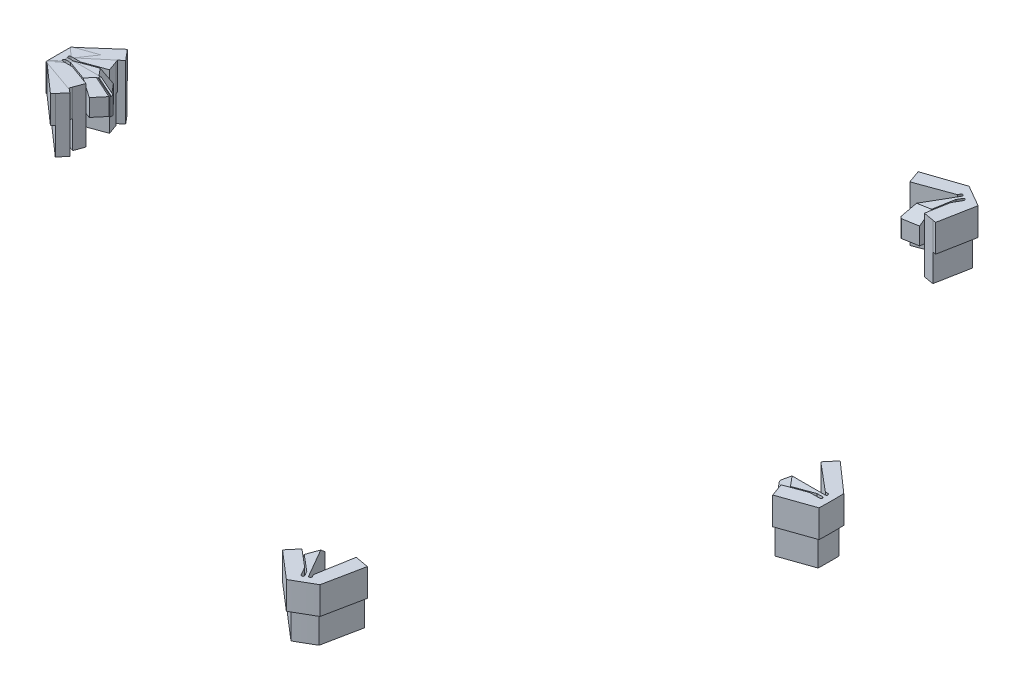
SolidWorks part; units mm, degrees
ref_plane "前视基准面" through (0, 0, 0) normal (0, 0, 1) x (1, 0, 0)
ref_plane "上视基准面" through (0, 0, 0) normal (0, 1, 0) x (1, 0, 0)
ref_plane "右视基准面" through (0, 0, 0) normal (1, 0, 0) x (0, 0, -1)
other "Configuration Table"
sketch "草图1" plane through (0, 0, 0) normal (0, 1, 0) x (1, 0, 0)
  line L0 (-106.6702, 0) -> (227.8, 0) construction
  line L1 (97, 0) -> (109.5607, 0) construction
  line L2 (109.5607, 0) -> (99.9387, 3.5022) construction
  line L3 (109.5607, 0) -> (99.9387, 8.0739) construction
  line L4 (99.9387, 8.0739) -> (99.9387, 3.5022) construction
  line L5 (109.5607, 0) -> (99.9387, -3.5022) construction
  line L6 (97, 0) -> (99.9387, -3.5022)
  line L7 (97, 0) -> (97, 0.4)
  line L8 (97, 0.4) -> (109.5607, 0.4)
  line L9 (109.5607, 0.4) -> (109.5607, 0) construction
  line L10 (109.5607, 0) -> (109.5607, -0.4) construction
  line L11 (109.5607, -0.4) -> (108.4618, -0.4)
  line L12 (109.5607, 0.4) -> (110.3607, 0.4)
  line L13 (110.3607, 0.4) -> (110.3607, -0.4)
  line L14 (110.3607, -0.4) -> (109.5607, -0.4)
  line L15 (108.4618, -0.4) -> (99.9387, -3.5022)
  circle A0 centre (0, 0) radius 97 construction
  circle A1 centre (0, 0) radius 100 construction
  circle A2 centre (109.5607, 0) radius 12.5607 construction
  circle A3 centre (109.5607, 0) radius 10.2396 construction
  dimension "D1" = 200
  dimension "D2" = 194
  dimension "D3" = 20
  dimension "D4" = 20
  dimension "D5" = 20
  dimension "D6" = 0.4
  dimension "D7" = 0.8
extrude "凸台-拉伸1" add sketch "草图1" along normal blind 8
sketch "草图2" plane through (0, 0, 0) normal (0, 1, 0) x (1, 0, 0)
  line L0 (115.245, 0) -> (-162.7444, 0) construction
  line L1 (108.4618, -0.4) -> (109.5607, 0) construction
  line L2 (99.9387, -3.5022) -> (108.4618, -0.4) construction
  line L3 (109.5607, 0) -> (101.1351, 7.0699) construction
  line L4 (100.981, 8.1131) -> (109.2196, 1.2)
  line L5 (109.2196, 1.2) -> (110.3607, 1.2) construction
  line L6 (110.3607, 1.2) -> (110.3607, -1.2) construction
  line L7 (110.3607, -1.2) -> (107.1409, -1.2) construction
  line L8 (107.1409, -1.2) -> (100.981, -3.442)
  line L9 (100.981, -3.442) -> (102.007, -6.2611)
  line L10 (102.007, -6.2611) -> (111.3203, -2.9997)
  line L12 (111.3203, 2.9997) -> (102.9093, 10.4112)
  line L13 (102.9093, 10.4112) -> (100.981, 8.1131)
  line L14 (107.1409, -1.2) -> (109.9607, -1.2)
  line L15 (110.3607, 0.4) -> (97, 0.4) construction
  line L16 (108.4618, -0.4) -> (110.3607, -0.4) construction
  line L17 (109.9607, -0.4) -> (110.3607, -0.4)
  line L18 (110.3607, -0.4) -> (110.3607, 0.4)
  line L19 (110.3607, 0.4) -> (109.9607, 0.4)
  line L20 (109.9607, 1.2) -> (109.2196, 1.2)
  line L21 (111.3607, 0) -> (110.3607, 0) construction
  arc A2 (109.9607, 1.2) -> (109.9607, 0.4) centre (109.9607, 0.8) cw
  arc A3 (109.9607, -0.4) -> (109.9607, -1.2) centre (109.9607, -0.8) cw
  arc A4 (111.3203, -2.9997) -> (111.3203, 2.9997) centre (0, 0) ccw
  circle A5 centre (111.3607, 0) radius 3 construction
  dimension "D10" = 6
  dimension "D1" = 0.7
  dimension "D2" = 0.3
  dimension "D3" = 0.8
  dimension "D4" = 0.8
  dimension "D5" = 1
  dimension "D6" = 3
  dimension "D7" = 3
  dimension "D8" = 1
  dimension "D9" = 40
extrude "凸台-拉伸2" add sketch "草图2" along normal blind 8 and the other way blind 8
sketch "草图4" plane through (12.8162, 0, 35.2121) normal (0.342, 0, 0.9397) x (0.9397, 0, -0.342)
  line L0 (92.7138, 5) -> (95.7138, 8)
  line L1 (92.7138, 8) -> (92.7138, 0) construction
  line L2 (92.7138, 8) -> (101.7839, 8) construction
  line L3 (95.7138, 8) -> (92.7138, 8)
  line L4 (92.7138, 8) -> (92.7138, 5)
  dimension "D1" = 5
  dimension "D2" = 45
extrude "切除-拉伸1" cut sketch "草图4" along direction (0.6428, 0, 0.766) on the side against the normal up to surface (3.7545 mm away) up to face at (103.4804, 4, -0.4)
ref_plane "基准面1" through (88.9113, 0, -31.1355) normal (0.9438, 0, -0.3305) x (0, 1, 0)
sketch "草图10" plane through (88.9113, 0, -31.1355) normal (0.9438, 0, -0.3305) x (0, 1, 0)
  line L0 (0, 34.5946) -> (0, 48.0374) construction
  line L1 (0, 32.0591) -> (0, 36.3357) construction
  line L3 (-8, 39.6233) -> (8, 39.6233) construction
  line L4 (0, 40.6233) -> (0, 39.6233)
  line L5 (0, 39.6233) -> (8, 39.6233)
  line L6 (8, 39.6233) -> (8, 40.6233)
  line L7 (8, 40.6233) -> (0, 40.6233)
  point P9 (7.8834, 39.6233)
  point P12 (0, 0)
  dimension "D2" = 1
sketch "草图11" plane through (0, 0, 0) normal (0, 1, 0) x (1, 0, 0)
  line L0 (111.3203, 2.9997) -> (102.9093, 10.4112) construction
  line L1 (102.007, -6.2611) -> (111.3203, -2.9997) construction
  line L2 (111.3203, 2.9997) -> (102.9093, 10.4112)
  line L3 (102.007, -6.2611) -> (111.3203, -2.9997)
  arc A0 (111.3203, -2.9997) -> (111.3203, 2.9997) centre (0, 0) ccw construction
  arc A1 (111.3203, -2.9997) -> (111.3203, 2.9997) centre (0, 0) ccw
sweep "扫描1" add profiles "草图10" path "草图11"
sketch "草图5" plane through (0, 8, 0) normal (0, 1, 0) x (1, 0, 0)
  line L0 (107.9333, 2.2794) -> (107.2492, 0.4)
  line L1 (100.981, 8.1131) -> (109.2196, 1.2) construction
  line L2 (109.9607, 0.4) -> (100.3444, 0.4) construction
  line L3 (107.2492, 0.4) -> (100.3444, 0.4)
  line L4 (100.3444, 0.4) -> (102.6439, 6.7177)
  line L5 (102.6439, 6.7177) -> (107.9333, 2.2794)
  dimension "D1" = 2
  dimension "D2" = 0
extrude "凸台-拉伸3" [suppressed] add sketch "草图5" against normal blind 0.8
sketch "草图6" [suppressed] plane through (94.5749, 0, 34.4225) normal (0.9397, 0, 0.342) x (0.342, 0, -0.9397)
  line L0 (38.0738, 8) -> (38.0738, 7.0693) construction
  line L1 (40.8926, 8) -> (35.255, 8) construction
  line L2 (37.0573, 7.2) -> (39.0573, 7.2) construction
  line L5 (37.3738, 7.2) -> (38.7738, 7.2)
  line L6 (37.8738, 7.7) -> (38.2738, 7.7)
  line L7 (37.8738, 7.7) -> (37.3738, 7.2)
  line L8 (38.2738, 7.7) -> (38.7738, 7.2)
  dimension "D1" = 0.4
  dimension "D2" = 0.3
  dimension "D3" = 135
extrude "切除-拉伸2" [suppressed] cut sketch "草图6" against normal up to next
mirror "镜向3" about plane through (0, 0, 0) normal (1, 0, 0) of bodies 115 107
mirror "镜向4" about plane through (0, 0, 0) normal (0, 0, 1) of bodies 108
sketch "草图3" plane through (0, 0, 0) normal (0, 0, 1) x (1, 0, 0)
  line L0 (0, 0) -> (0, 86.329) construction
pattern_circular "阵列(圆周)1" count 3 over 360 about axis through (0, 0, 0) along (0, 1, 0) reverse direction yes of bodies 109
